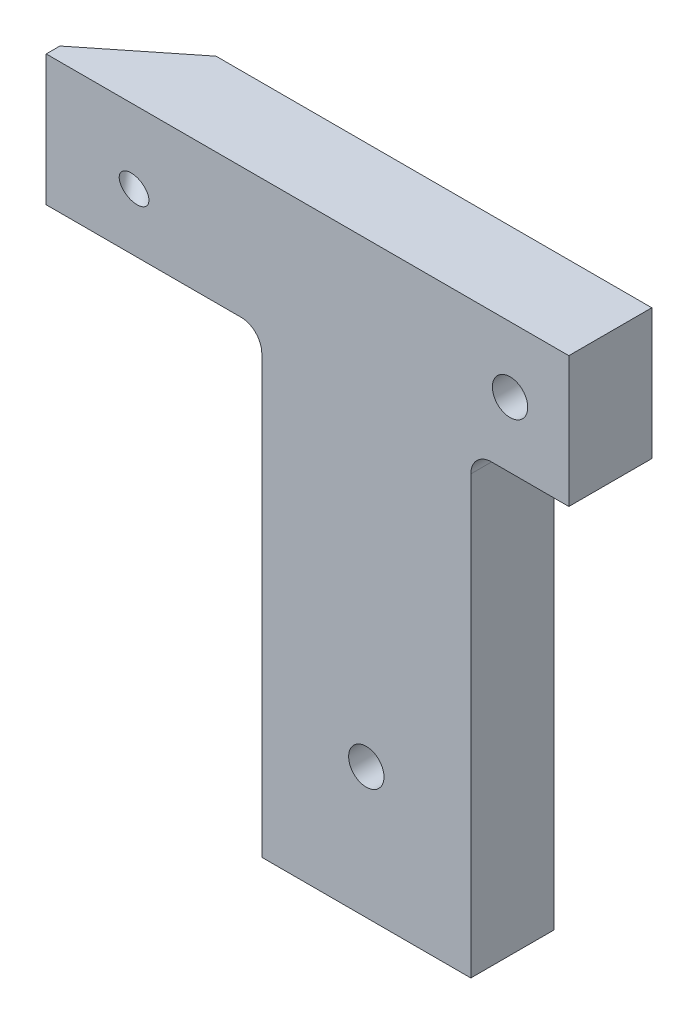
SolidWorks part; units mm, degrees
other "Markup1"
sketch "Sketch12" plane through (40, 0, 0) normal (0.1663, -0.0186, -0.9859) x (0.442, -0.8924, 0.0914)
material "6061-T4 (SS)"
ref_plane "Front Plane" through (0, 0, 0) normal (0, 0, 1) x (1, 0, 0)
ref_plane "Top Plane" through (0, 0, 0) normal (0, 1, 0) x (1, 0, 0)
ref_plane "Right Plane" through (0, 0, 0) normal (1, 0, 0) x (0, 0, -1)
sketch "Sketch1" plane through (0, 0, 0) normal (0, 0, 1) x (1, 0, 0)
  line L1 (0, 0) -> (40, 0)
  line L2 (0, 0) -> (0, 45)
  line L3 (0, 45) -> (40, 45)
  line L4 (40, 0) -> (40, 45)
  dimension "D1" = 40
  dimension "D2" = 45
extrude "Boss-Extrude1" add sketch "Sketch1" along normal blind 6.35
ref_plane "Plane1" through (-7.1054, 3.0997, -8.9102) normal (-0.6016, 0.2625, -0.7544) x (-0.7988, -0.1977, 0.5682)
sketch "Sketch4" plane through (-7.1054, 3.0997, -8.9102) normal (-0.6016, 0.2625, -0.7544) x (-0.7988, -0.1977, 0.5682)
  line L5 (1.1047, 52.5016) -> (-18.8953, 52.5016)
  line L6 (1.1047, 52.5016) -> (1.1047, 32.5016)
  line L7 (1.1047, 32.5016) -> (-18.8953, 32.5016)
  line L8 (-18.8953, 52.5016) -> (-18.8953, 32.5016)
  line L9 (1.1047, 52.5016) -> (-18.8953, 32.5016) construction
  line L10 (1.1047, 32.5016) -> (-18.8953, 52.5016) construction
  point P0 (-8.8953, 42.5016)
  dimension "D1" = 20
extrude "Cut-Extrude1" cut sketch "Sketch4" against normal blind 4 contours L8 L7 L6 L5
sketch "Sketch7" plane through (0, 0, 0) normal (0, 0, -1) x (-1, 0, 0)
  line L0 (-16.5, -34.35) -> (-16.5, -28) construction
  line L1 (0, 0) -> (-16.5, 0)
  line L2 (0, 0) -> (0, 35)
  line L3 (0, 35) -> (-14.9125, 35)
  line L4 (-16.5, 0) -> (-16.5, 33.4125)
  line L5 (0, 0) -> (-40, 0) construction
  line L6 (-40, 0) -> (-32.5, 0)
  line L7 (-40, 0) -> (-40, 35)
  line L8 (-40, 35) -> (-34.0875, 35)
  line L9 (-32.5, 0) -> (-32.5, 33.4125)
  line L10 (-32.5, -28) -> (-32.5, 21.4125) construction
  line L11 (-40, 0) -> (-40, 45) construction
  arc A0 (-14.9125, 35) -> (-16.5, 33.4125) centre (-14.9125, 33.4125) ccw
  arc A1 (-34.0875, 35) -> (-32.5, 33.4125) centre (-34.0875, 33.4125) cw
  point P9 (-16.5, 35)
  dimension "D2" = 1.5875
  dimension "D3" = 1.5875
  dimension "D1" = 35
extrude "Cut-Extrude2" cut sketch "Sketch7" against normal blind 19
hole_wizard "#2-56 Tapped Hole1" positions "Sketch8" profile "Sketch9" tap size "#2-56" standard "ANSI Inch" end condition through all
sketch "Sketch8" plane through (-4.699, 2.0499, -5.8925) normal (-0.6016, 0.2625, -0.7544) x (-0.7988, -0.1977, 0.5682)
  point P0 (-9.5556, 39.3183)
sketch "Sketch9" plane through (2.9339, 41.0742, 1.5966) normal (0.6739, 0.6739, -0.3029) x (-0.4289, 0.6907, 0.5823)
  line L0 (0, 0) -> (0, 36.666)
  line L1 (0, 36.666) -> (0.889, 36.666)
  line L2 (0.889, 36.666) -> (0.889, 0)
  line L5 (0.889, 0) -> (0, 0)
  line L11 (0, -6.35) -> (0, 107.95) construction
  dimension "Thru Tap Drill Dia." = 1.778
  dimension "Thru Tap Drill Depth" = 36.666
cosmetic thread "Hole Thread2" parameters "D2"=2.1844
hole_wizard "CBORE for #2 Socket Head Cap Screw1" positions "Sketch10" profile "Sketch11" counterbore size "#2" standard "ANSI Inch" end condition through all
sketch "Sketch10" plane through (0, 0, 0) normal (0, 0, -1) x (-1, 0, 0)
  point P0 (-24.5, 10)
  point P7 (-35.5, 40)
sketch "Sketch11" plane through (24.5, 10, 0) normal (1, 0, 0) x (0, 1, 0)
  line L0 (0, 0) -> (0, 6.35)
  line L1 (0, 6.35) -> (1.3525, 6.35)
  line L3 (1.3525, 6.35) -> (1.3525, 3.6844)
  line L4 (1.3525, 3.6844) -> (2.3812, 3.6844)
  line L5 (2.3812, 3.6844) -> (2.3812, 0)
  line L7 (2.3812, 0) -> (0, 0)
  line L11 (0, -6.35) -> (0, 107.95) construction
  dimension "Thru Hole Dia." = 2.7051
  dimension "Thru Hole Depth" = 6.35
  dimension "C'Bore Dia." = 4.7625
  dimension "C'Bore Depth" = 3.6844
